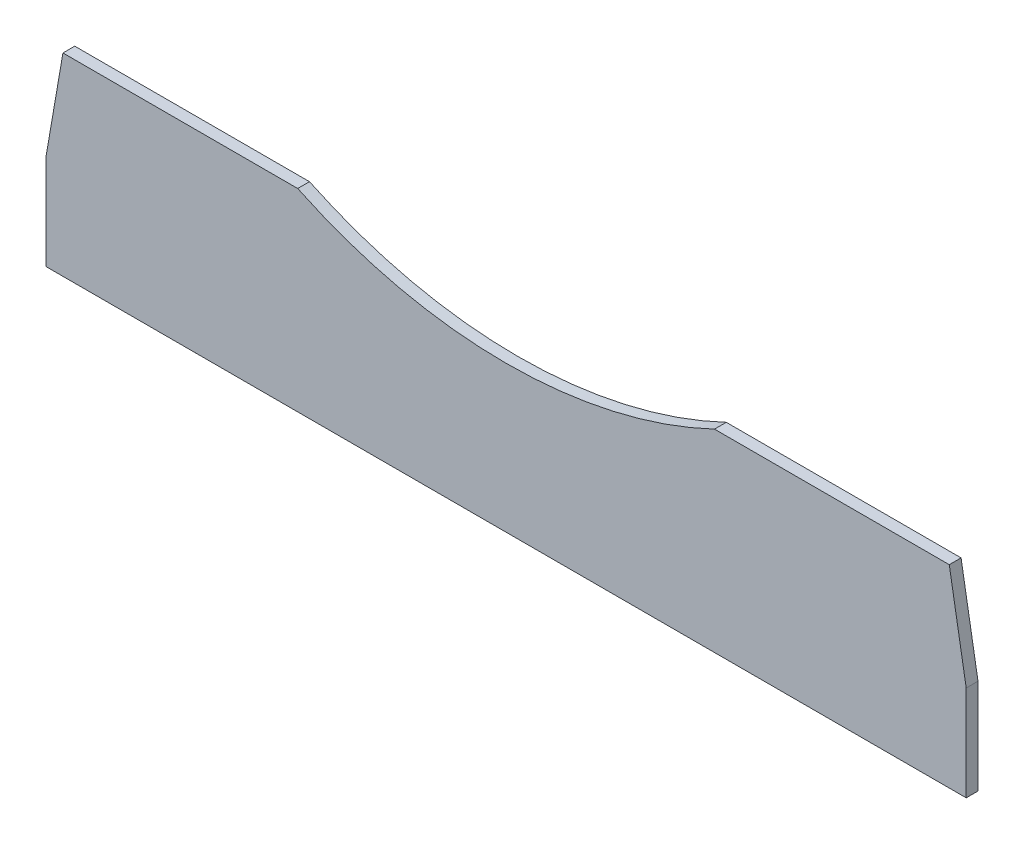
SolidWorks part; units mm, degrees
ref_plane "前视基准面" through (0, 0, 0) normal (0, 0, 1) x (1, 0, 0)
ref_plane "上视基准面" through (0, 0, 0) normal (0, 1, 0) x (1, 0, 0)
ref_plane "右视基准面" through (0, 0, 0) normal (1, 0, 0) x (0, 0, -1)
other "Configuration Table"
sketch "草图1" plane through (0, 0, 0) normal (0, 0, 1) x (1, 0, 0)
  line L0 (0, 0) -> (80, 0) construction
  line L1 (80, 0) -> (80, 9.153) construction
  line L2 (80, 9.153) -> (78.4064, 18.4) construction
  line L3 (78.4064, 18.4) -> (1.5936, 18.4) construction
  line L4 (1.5936, 18.4) -> (0, 9.153) construction
  line L5 (0, 9.153) -> (0, 0) construction
  line L6 (40, 54.4) -> (40, 18.4) construction
  line L7 (77.564, 17.4) -> (57.6635, 17.4)
  line L8 (2.436, 17.4) -> (1, 9.0674)
  line L9 (1, 9.0674) -> (1, 1)
  line L10 (1, 1) -> (79, 1)
  line L11 (79, 1) -> (79, 9.0674)
  line L12 (79, 9.0674) -> (77.564, 17.4)
  line L13 (22.3365, 17.4) -> (2.436, 17.4)
  line L14 (77.564, 17.4) -> (2.436, 17.4) construction
  circle A0 centre (40, 54.4) radius 42 construction
  arc A1 (22.3365, 17.4) -> (57.6635, 17.4) centre (40, 54.4) ccw
  circle A2 centre (40, 54.4) radius 41 construction
  dimension "D7" = 84
  dimension "D1" = 80
  dimension "D2" = 9.153
  dimension "D3" = 9.153
  dimension "D4" = 9.3834
  dimension "D5" = 9.3834
  dimension "D6" = 76.8129
  dimension "D8" = 36
  dimension "D9" = 1
extrude "凸台-拉伸1" add sketch "草图1" along normal blind 1
sketch "草图2" plane through (0, 0, 0) normal (0, 0, -1) x (-1, 0, 0)
  line L0 (-79, 9.0674) -> (-1, 9.0674) construction
  line L1 (-1, 9.0674) -> (-1, 1) construction
  text T0 "PART 4" font "Arial Narrow" height 4
extrude "凸台-拉伸2" add sketch "草图2" along normal blind 0.2
